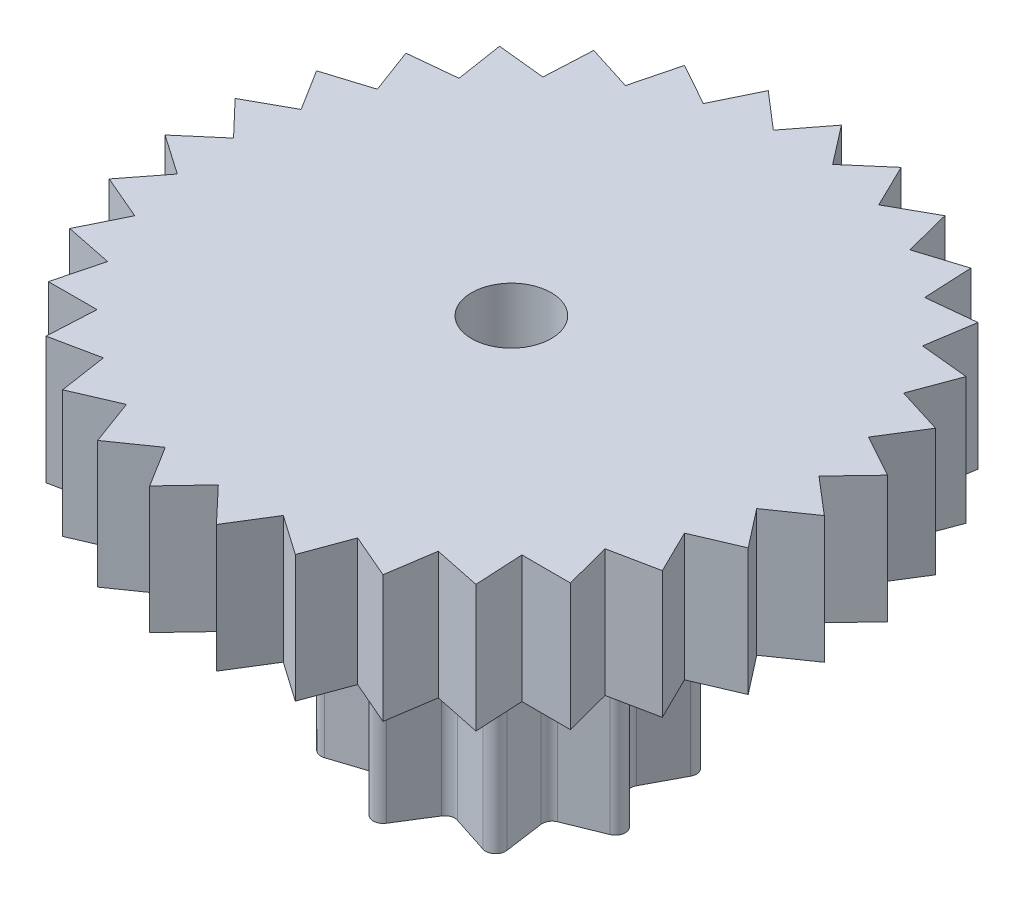
SolidWorks part; units mm, degrees
ref_plane "Front Plane" through (0, 0, 0) normal (0, 0, 1) x (1, 0, 0)
ref_plane "Top Plane" through (0, 0, 0) normal (0, 1, 0) x (1, 0, 0)
ref_plane "Right Plane" through (0, 0, 0) normal (1, 0, 0) x (0, 0, -1)
sketch "Sketch1" plane through (0, 0, 0) normal (0, 0, 1) x (1, 0, 0)
  line L0 (-6.625, 7.4) -> (-6.625, 4.85)
  line L1 (-6.625, 4.85) -> (-2.95, 4.85)
  line L2 (-2.95, 4.85) -> (-2.95, 0)
  line L3 (-2.95, 0) -> (0, 0)
  line L4 (-6.625, 7.4) -> (0, 7.4)
  line L5 (0, 7.4) -> (0, 0) construction
  line L6 (0, 0) -> (0, 7.4)
  dimension "D1" = 6.625
  dimension "D2" = 2.55
  dimension "D3" = 7.4
  dimension "D4" = 2.95
revolve "Revolve1" add sketch "Sketch1" angle 360 about L5
sketch "Sketch2" plane through (0, 7.4, 0) normal (0, 1, 0) x (1, 0, 0)
  circle A0 centre (0, 0) radius 0.8
  dimension "D1" = 1.6
extrude "Cut-Extrude1" cut sketch "Sketch2" against normal through all
ref_axis "Axis1" through (0, 0, 0) along (0, 1, 0)
sketch "Sketch4" plane through (0, 7.4, 0) normal (0, 1, 0) x (1, 0, 0)
  line L0 (0, 0) -> (0, 6.625) construction
  line L1 (0, 0) -> (0.6702, 6.591) construction
  line L2 (0, 0) -> (1.3336, 6.4894) construction
  line L3 (1.3336, 6.4894) -> (0.5952, 5.853)
  line L4 (0.5952, 5.853) -> (0, 6.625)
  circle A0 centre (0, 0) radius 6.625 construction
  arc A1 (0, 6.625) -> (1.3336, 6.4894) centre (0, 0) cw
  circle A2 centre (0, 0) radius 5.8832 construction
  dimension "D1" = 11.613
extrude "Cut-Extrude2" cut sketch "Sketch4" against normal through all
pattern_circular "CirPattern1" count 31 over 360 about axis through (0, 0, 0) along (0, 1, 0) of "Cut-Extrude2"
sketch "Sketch5" plane through (0, 0, 0) normal (0, -1, 0) x (1, 0, 0)
  line L0 (0, 0) -> (0, 2.95) construction
  line L1 (0, 0) -> (1.8962, 2.2598) construction
  line L2 (0, 0) -> (1.009, 2.7721) construction
  line L3 (0, 2.95) -> (0.6791, 1.8658)
  line L4 (0.6791, 1.8658) -> (1.8962, 2.2598)
  circle A0 centre (0, 0) radius 1.9855 construction
  circle A1 centre (0, 0) radius 2.95 construction
  circle A2 centre (0, 0) radius 2.95 construction
  arc A3 (0, 2.95) -> (1.8962, 2.2598) centre (0, 0) cw
  dimension "D1" = 40
extrude "Cut-Extrude3" cut sketch "Sketch5" against normal up to surface (4.85 mm away) up to face at (0, 4.85, 0)
pattern_circular "CirPattern2" count 9 over 360 about axis through (0, 0, 0) along (0, 1, 0) of "Cut-Extrude3"
fillet "Fillet1" radius 0.2 17 edges at (0, 2.425, 2.95) (-1.7195, 2.425, 0.9928) (-1.9554, 2.425, -0.3448) (1.7195, 2.425, 0.9928) (1.9554, 2.425, -0.3448) (-1.2763, 2.425, -1.521) (0, 2.425, -1.9855) (-1.009, 2.425, -2.7721) (1.009, 2.425, -2.7721) (2.5548, 2.425, -1.475) (2.9052, 2.425, 0.5123) (-2.5548, 2.425, -1.475) (-2.9052, 2.425, 0.5123) (-0.6791, 2.425, 1.8658) (-1.8962, 2.425, 2.2598) (0.6791, 2.425, 1.8658) (1.8962, 2.425, 2.2598)
